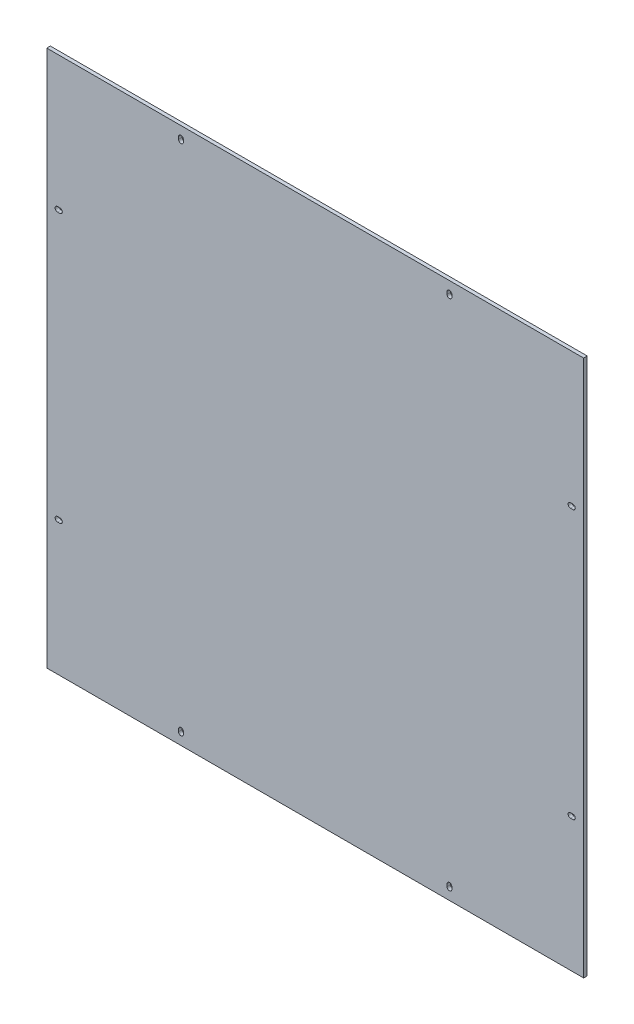
SolidWorks part; units mm, degrees
ref_plane "Piano frontale" through (0, 0, 0) normal (0, 0, 1) x (1, 0, 0)
ref_plane "Piano superiore" through (0, 0, 0) normal (0, 1, 0) x (1, 0, 0)
ref_plane "Piano destro" through (0, 0, 0) normal (1, 0, 0) x (0, 0, -1)
sketch "Schizzo1" plane through (0, 0, 0) normal (0, 0, 1) x (1, 0, 0)
  line L0 (10, 448) -> (10, -28.2593) construction
  line L1 (0, 0) -> (448, 0)
  line L2 (0, 0) -> (0, 448)
  line L3 (0, 448) -> (448, 448)
  line L4 (448, 0) -> (448, 448)
  line L5 (0, 224) -> (448, 224) construction
  line L6 (224, 448) -> (224, 0) construction
  line L7 (438, 448) -> (438, -28.2593) construction
  line L8 (0, 438) -> (525.0128, 438) construction
  line L9 (0, 10) -> (525.0128, 10) construction
  line L10 (0, 448) -> (0, 224) construction
  line L11 (0, 448) -> (0, 224) construction
  line L12 (9, 336) -> (11, 336) construction
  line L13 (9, 338) -> (11, 338)
  line L14 (9, 334) -> (11, 334)
  line L15 (0, 336) -> (224, 336) construction
  line L16 (9, 112) -> (11, 112) construction
  line L17 (9, 110) -> (11, 110)
  line L18 (9, 114) -> (11, 114)
  line L19 (439, 112) -> (437, 112) construction
  line L20 (439, 110) -> (437, 110)
  line L21 (439, 114) -> (437, 114)
  line L22 (439, 336) -> (437, 336) construction
  line L23 (439, 338) -> (437, 338)
  line L24 (439, 334) -> (437, 334)
  line L25 (112, 448) -> (112, 224) construction
  line L26 (112, 439) -> (112, 437) construction
  line L27 (114, 439) -> (114, 437)
  line L28 (110, 439) -> (110, 437)
  line L29 (336, 439) -> (336, 437) construction
  line L30 (334, 439) -> (334, 437)
  line L31 (338, 439) -> (338, 437)
  line L32 (112, 9) -> (112, 11) construction
  line L33 (114, 9) -> (114, 11)
  line L34 (110, 9) -> (110, 11)
  line L35 (336, 9) -> (336, 11) construction
  line L36 (334, 9) -> (334, 11)
  line L37 (338, 9) -> (338, 11)
  line L38 (36.9588, 287.1268) -> (36.9588, 448) construction
  line L57 (237.6695, 19.3283) -> (237.6695, 174.7416) construction
  line L58 (336, 27.7675) -> (336, 161.4481) construction
  line L61 (224, 27.7675) -> (448, 27.7675) construction
  line L65 (224, 224) -> (448, 224) construction
  arc A0 (9, 338) -> (9, 334) centre (9, 336) ccw
  arc A1 (11, 334) -> (11, 338) centre (11, 336) ccw
  arc A2 (9, 110) -> (9, 114) centre (9, 112) cw
  arc A3 (11, 114) -> (11, 110) centre (11, 112) cw
  arc A4 (439, 110) -> (439, 114) centre (439, 112) ccw
  arc A5 (437, 114) -> (437, 110) centre (437, 112) ccw
  arc A6 (439, 338) -> (439, 334) centre (439, 336) cw
  arc A7 (437, 334) -> (437, 338) centre (437, 336) cw
  arc A8 (114, 439) -> (110, 439) centre (112, 439) ccw
  arc A9 (110, 437) -> (114, 437) centre (112, 437) ccw
  arc A10 (334, 439) -> (338, 439) centre (336, 439) cw
  arc A11 (338, 437) -> (334, 437) centre (336, 437) cw
  arc A12 (114, 9) -> (110, 9) centre (112, 9) cw
  arc A13 (110, 11) -> (114, 11) centre (112, 11) cw
  arc A14 (334, 9) -> (338, 9) centre (336, 9) ccw
  arc A15 (338, 11) -> (334, 11) centre (336, 11) ccw
  point P19 (10, 336)
  point P28 (10, 112)
  point P35 (438, 112)
  point P42 (438, 336)
  point P49 (112, 438)
  point P52 (112, 438)
  point P59 (336, 438)
  point P66 (112, 10)
  point P73 (336, 10)
  point P82 (253.9707, 256)
  point P89 (253.9707, 224)
  point P96 (253.9707, 192)
  point P103 (253.9707, 384)
  point P110 (253.9707, 352)
  point P117 (253.9707, 320)
  point P141 (253.9707, 288)
  point P148 (253.9707, 160)
  point P155 (253.9707, 128)
  point P162 (253.9707, 96)
  point P169 (253.9707, 64)
  point P179 (280.1758, 232.4048)
  point P193 (280.1085, 282.4047)
  point P207 (280.0413, 332.4047)
  dimension "D5" = 1
  dimension "D1" = 448
  dimension "D2" = 448
  dimension "D3" = 10
  dimension "D4" = 10
  dimension "D6" = 4
  dimension "D7" = 112
  dimension "D8" = 112
  dimension "D9" = 1
  dimension "D10" = 4
extrude "Estrusione-Estrusione1" add sketch "Schizzo1" against normal blind 3
